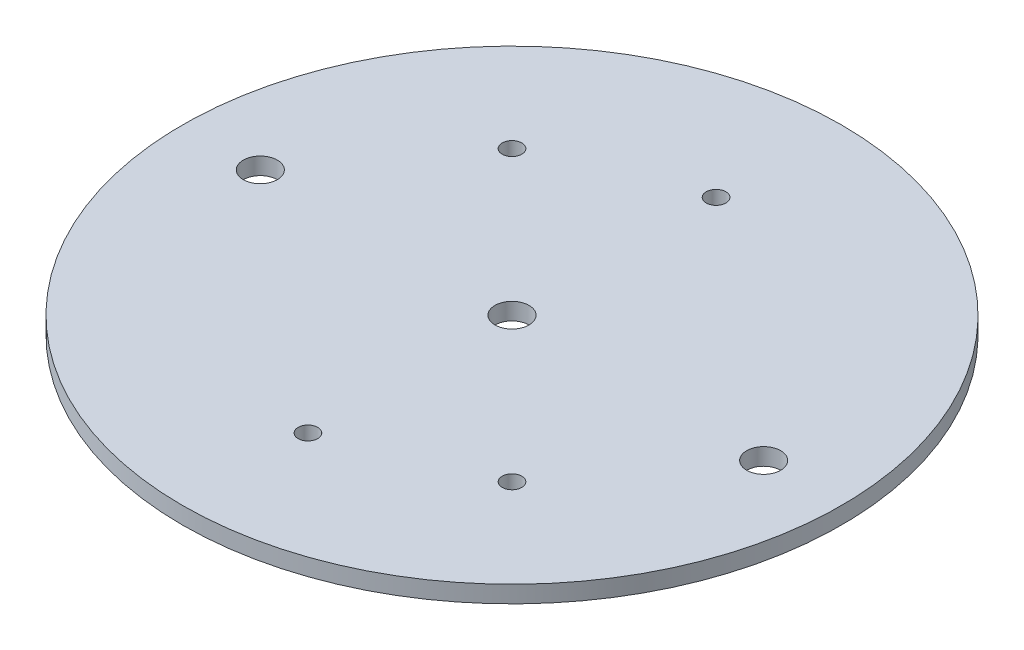
SolidWorks part; units mm, degrees
ref_plane "Front Plane" through (0, 0, 0) normal (0, 0, 1) x (1, 0, 0)
ref_plane "Top Plane" through (0, 0, 0) normal (0, 1, 0) x (1, 0, 0)
ref_plane "Right Plane" through (0, 0, 0) normal (1, 0, 0) x (0, 0, -1)
sketch "Sketch2" plane through (0, 0, 0) normal (0, 1, 0) x (1, 0, 0)
  line L0 (-46.99, 0) -> (46.99, 0) construction
  line L1 (0, -38.1) -> (0, 38.1) construction
  line L2 (-26.9408, 26.9408) -> (26.9408, -26.9408) construction
  circle A0 centre (0, 0) radius 61.5315
  circle A1 centre (-46.99, 0) radius 3.175
  circle A2 centre (46.99, 0) radius 3.175
  circle A3 centre (0, 0) radius 3.175
  circle A4 centre (0, 38.1) radius 1.8288
  circle A5 centre (0, -38.1) radius 1.8288
  circle A8 centre (-26.9408, 26.9408) radius 1.8288
  circle A9 centre (26.9408, -26.9408) radius 1.8288
  point P6 (0, 0)
  point P12 (0, 0)
  point P17 (0, 0)
  point P18 (0, 0)
  dimension "D1" = 123.063
  dimension "D3" = 6.35
  dimension "D4" = 6.35
  dimension "D5" = 3.6576
  dimension "D6" = 76.2
  dimension "D8" = 45
  dimension "D2" = 93.98
  dimension "D7" = 76.2
extrude "Boss-Extrude1" add sketch "Sketch2" along normal blind 3.175
